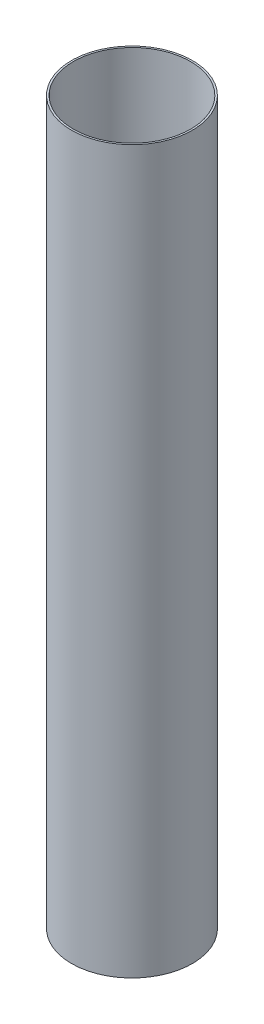
SolidWorks part; units mm, degrees
ref_plane "Front Plane" through (0, 0, 0) normal (0, 0, 1) x (1, 0, 0)
ref_plane "Top Plane" through (0, 0, 0) normal (0, 1, 0) x (1, 0, 0)
ref_plane "Right Plane" through (0, 0, 0) normal (1, 0, 0) x (0, 0, -1)
sketch "Sketch1" plane through (0, 0, 0) normal (0, 1, 0) x (1, 0, 0)
  circle A0 centre (0, 0) radius 65
  circle A1 centre (0, 0) radius 67
  dimension "D1" = 130
  dimension "D2" = 134
extrude "Boss-Extrude1" add sketch "Sketch1" along normal mid plane 800
